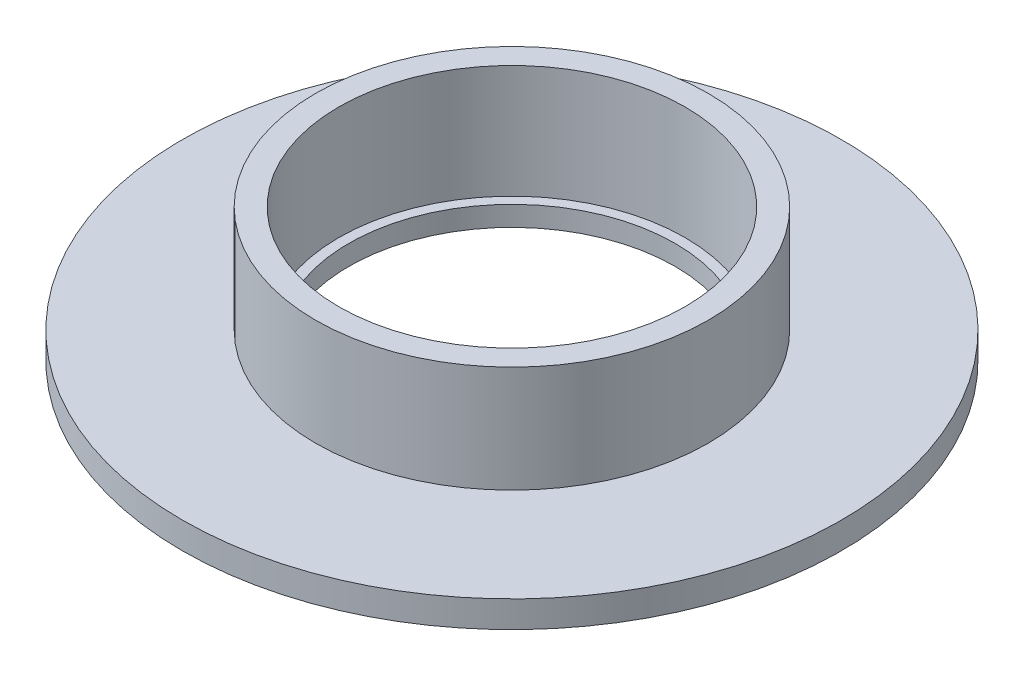
SolidWorks part; units mm, degrees
ref_plane "Спереди" through (0, 0, 0) normal (0, 0, 1) x (1, 0, 0)
ref_plane "Сверху" through (0, 0, 0) normal (0, 1, 0) x (1, 0, 0)
ref_plane "Справа" through (0, 0, 0) normal (1, 0, 0) x (0, 0, -1)
sketch "Эскиз1" plane through (0, 0, 0) normal (0, 1, 0) x (1, 0, 0)
  circle A0 centre (0, 0) radius 24.5
  circle A1 centre (0, 0) radius 49.5
  dimension "D1" = 99
  dimension "D2" = 49
extrude "Бобышка-Вытянуть2" add sketch "Эскиз1" along normal blind 3
sketch "Эскиз2" plane through (0, 3, 0) normal (0, 1, 0) x (1, 0, 0)
  circle A0 centre (0, 0) radius 26
  circle A1 centre (0, 0) radius 49.5
  dimension "D1" = 52
  dimension "D2" = 99
extrude "Бобышка-Вытянуть3" add sketch "Эскиз2" along normal blind 1
sketch "Эскиз3" plane through (0, 4, 0) normal (0, 1, 0) x (1, 0, 0)
  circle A0 centre (0, 0) radius 26
  circle A1 centre (0, 0) radius 29.5
  dimension "D1" = 59
  dimension "D2" = 52
extrude "Бобышка-Вытянуть4" add sketch "Эскиз3" along normal blind 16
